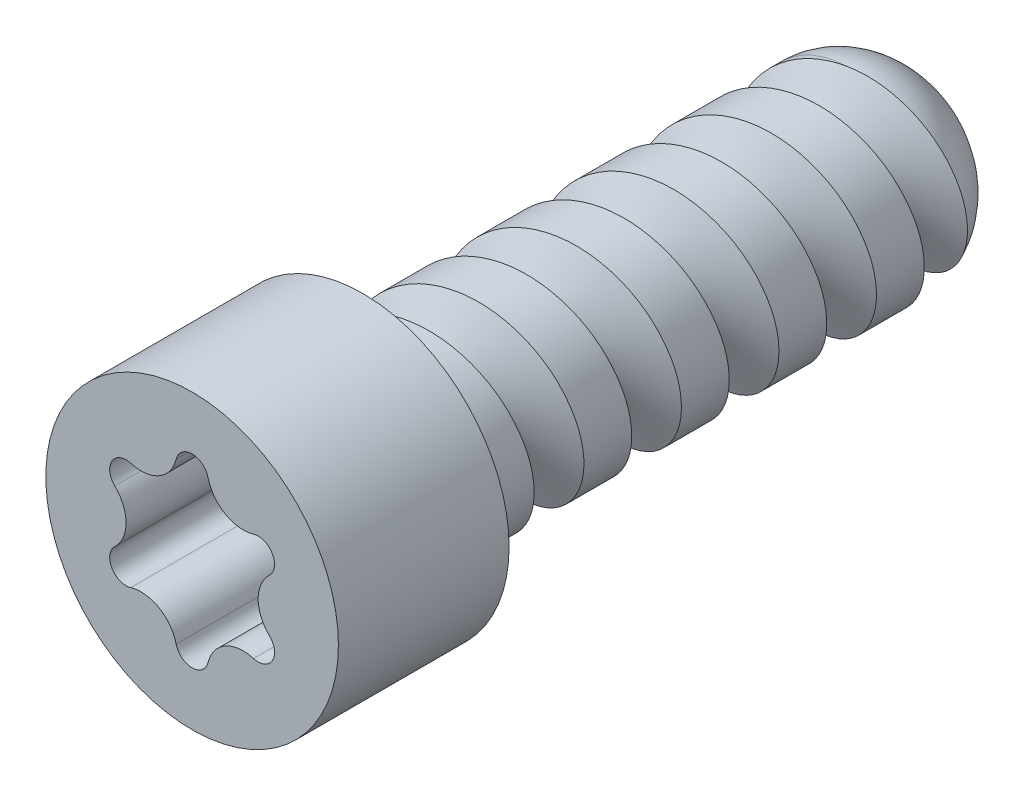
SolidWorks part; units mm, degrees
ref_plane "Front Plane" through (0, 0, 0) normal (0, 0, 1) x (1, 0, 0)
ref_plane "Top Plane" through (0, 0, 0) normal (0, 1, 0) x (1, 0, 0)
ref_plane "Right Plane" through (0, 0, 0) normal (1, 0, 0) x (0, 0, -1)
sketch "Sketch1" plane through (0, 0, 0) normal (0, 0, 1) x (1, 0, 0)
  circle A0 centre (0, 0) radius 2
  dimension "D1" = 4
extrude "Boss-Extrude1" add sketch "Sketch1" along normal blind 10
sketch "Sketch5" plane through (0, 0, 10) normal (0, 0, 1) x (1, 0, 0)
  circle A0 centre (0, 0) radius 2
  dimension "D1" = 4
curve "Helix/Spiral1" pitch 2 height 11.5 radius 2 centre (0, 0, 10) axis (0, 0, -1) start towards (1, 0, 0)
sketch "Sketch7" plane through (0, 0, 0) normal (0, 1, 0) x (1, 0, 0)
  line L0 (2, 0) -> (-2, 0) construction
  line L2 (0, 0) -> (-1.4061, -1.5) construction
  line L3 (0, 0) -> (0, 0.3491) construction
  line L4 (-1.4061, -1.5) -> (0, -3) construction
  line L5 (-1.4061, -1.5) -> (-1.6075, -1.5) construction
  line L6 (0, 1.6866) -> (0, 0)
  line L7 (0, 0) -> (-2, 0)
  ellipse E1 centre (0, 0) end of major axis (-2, 0) minor radius 1.6866 (-2, 0) -> (0, 1.6866) cw
revolve "Revolve1" add sketch "Sketch7" angle 360 about L3
sketch "Sketch4" plane through (0, 0, 0) normal (0, 1, 0) x (1, 0, 0)
  line L0 (2, -9.49) -> (2, -10.51)
  line L1 (2, -10) -> (2, 0) construction
  line L2 (2, -9.49) -> (0.9, -10)
  line L3 (-2, -10) -> (2, -10) construction
  line L4 (0.9, -10) -> (2, -10) construction
  line L5 (2, -10.51) -> (0.9, -10)
  dimension "D1" = 1.1
  dimension "D2" = 0.51
sweep "Cut-Sweep2" cut profiles "Sketch4" path "Helix/Spiral1" align with end faces yes
sketch "Sketch8" plane through (0, 0, 10) normal (0, 0, 1) x (1, 0, 0)
  circle A0 centre (0, 0) radius 3
  dimension "D1" = 6
extrude "Boss-Extrude2" add sketch "Sketch8" along normal blind 1
sketch "Sketch9" plane through (0, 0, 11) normal (0, 0, 1) x (1, 0, 0)
  line L0 (-0.3267, 1.6424) -> (0, 0) construction
  line L1 (0, 1.564) -> (-0.6772, 1.173) construction
  line L2 (0, 0) -> (0.802, 1.3891) construction
  line L3 (0, 0) -> (0.3267, 1.6424) construction
  line L4 (-0.3267, 1.6424) -> (0.3267, 1.6424) construction
  line L5 (-0.6772, 1.173) -> (0.6772, 1.173) construction
  line L6 (0.6772, 1.173) -> (0, 1.564) construction
  line L12 (-0.802, 1.3891) -> (0.802, -1.3891) construction
  circle A0 centre (0, 0) radius 3
  circle A1 centre (0, 0) radius 1.9 construction
  arc A2 (1.259, 1.1042) -> (1.5857, 0.5383) centre (1.3545, 0.782) cw
  arc A3 (-0.3267, 1.6424) -> (0.3267, 1.6424) centre (0, 1.564) cw
  arc A4 (0.3267, 1.6424) -> (0.6772, 1.173) centre (1.0483, 1.8157) ccw
  arc A5 (0.6772, 1.173) -> (1.259, 1.1042) centre (1.0483, 1.8157) ccw
  arc A6 (1.5857, 0.5383) -> (1.3545, 0) centre (2.0966, 0) ccw
  arc A7 (0.6772, 1.173) -> (-0.6772, 1.173) centre (0, 0) ccw construction
  arc A8 (1.5857, -0.5383) -> (1.259, -1.1042) centre (1.3545, -0.782) cw
  arc A9 (1.3545, 0) -> (1.5857, -0.5383) centre (2.0966, 0) ccw
  arc A10 (1.259, -1.1042) -> (0.6772, -1.173) centre (1.0483, -1.8157) ccw
  arc A11 (0.3267, -1.6424) -> (-0.3267, -1.6424) centre (0, -1.564) cw
  arc A12 (0.6772, -1.173) -> (0.3267, -1.6424) centre (1.0483, -1.8157) ccw
  arc A13 (-0.3267, -1.6424) -> (-0.6772, -1.173) centre (-1.0483, -1.8157) ccw
  arc A14 (-0.6772, 1.173) -> (-0.3267, 1.6424) centre (-1.0483, 1.8157) ccw
  circle A15 centre (0, 0) radius 3 construction
  arc A16 (-1.259, -1.1042) -> (-1.5857, -0.5383) centre (-1.3545, -0.782) cw
  arc A17 (-0.6772, -1.173) -> (-1.259, -1.1042) centre (-1.0483, -1.8157) ccw
  arc A18 (-1.5857, -0.5383) -> (-1.3545, 0) centre (-2.0966, 0) ccw
  arc A19 (-1.5857, 0.5383) -> (-1.259, 1.1042) centre (-1.3545, 0.782) cw
  arc A20 (-1.3545, 0) -> (-1.5857, 0.5383) centre (-2.0966, 0) ccw
  arc A21 (-1.259, 1.1042) -> (-0.6772, 1.173) centre (-1.0483, 1.8157) ccw
  point P56 (0, 0)
  circle M32 centre (0, 0) radius 3
  dimension "D1" = 3.8
  dimension "D2" = 6
extrude "Boss-Extrude3" add sketch "Sketch9" along normal blind 2.5 contours A19 A21 A14 A3 A4 A5 A2 A6 A9 A8 A10 A12 A11 A13 A17 A16 A18 A20 M32 region at (-2.9151, 0, 11)
